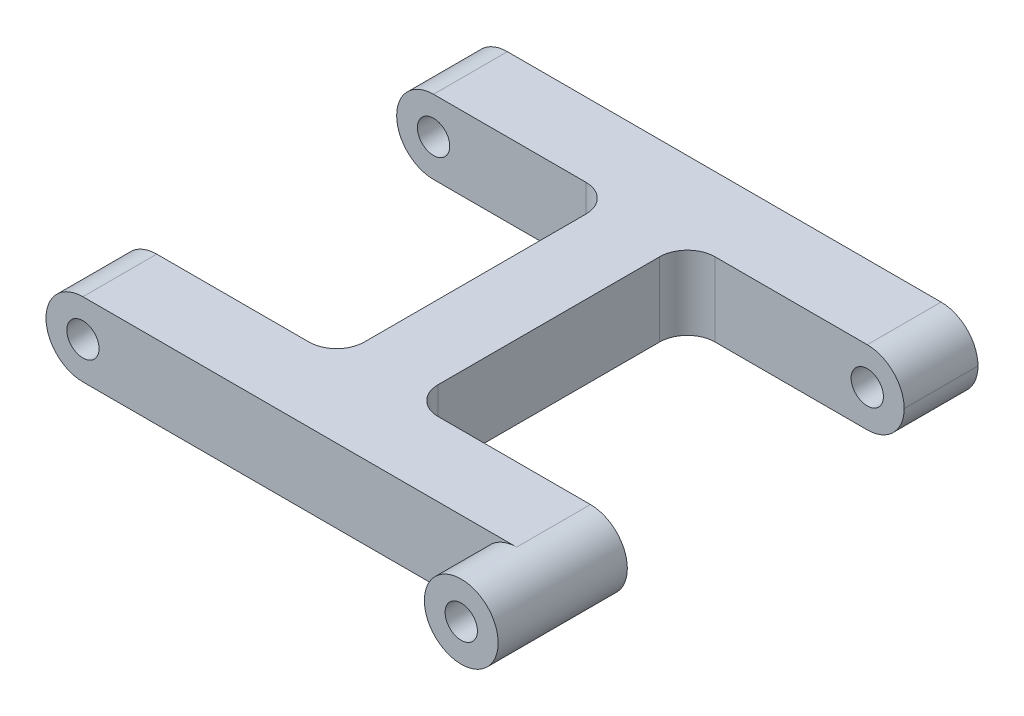
SolidWorks part; units mm, degrees
ref_plane "Alzado" through (0, 0, 0) normal (0, 0, 1) x (1, 0, 0)
ref_plane "Planta" through (0, 0, 0) normal (0, 1, 0) x (1, 0, 0)
ref_plane "Vista lateral" through (0, 0, 0) normal (1, 0, 0) x (0, 0, -1)
sketch "Croquis2" plane through (0, 0, 0) normal (0, 1, 0) x (1, 0, 0)
  line L5 (27.5, -23) -> (27.5, -15)
  line L6 (27.5, -15) -> (4, -15)
  line L7 (4, -15) -> (4, 15)
  line L8 (4, 15) -> (27.5, 15)
  line L9 (27.5, 15) -> (27.5, 23)
  line L24 (-35, 0) -> (35, 0) construction
  line L35 (27.5, 23) -> (-27.5, 23)
  line L36 (27.5, -23) -> (-27.5, -23)
  line L37 (-27.5, -23) -> (-27.5, -15)
  line L38 (-27.5, -15) -> (-4, -15)
  line L39 (-4, -15) -> (-4, 15)
  line L40 (-4, 15) -> (-27.5, 15)
  line L41 (-27.5, 15) -> (-27.5, 23)
  line L42 (0, 23) -> (0, -23) construction
  dimension "D1" = 55
  dimension "D2" = 55
  dimension "D3" = 4
  dimension "D4" = 4
  dimension "D5" = 8
  dimension "D6" = 8
  dimension "D7" = 23.5
  dimension "D8" = 30
  dimension "D9" = 30
extrude "Saliente-Extruir1" add sketch "Croquis2" along normal mid plane 8
sketch "Croquis3" plane through (0, 0, 23) normal (0, 0, 1) x (1, 0, 0)
  line L2 (-27.5, 4) -> (-27.5, -4) construction
  line L5 (27.5, 4) -> (27.5, -4) construction
  line L6 (-27.5, -4) -> (27.5, -4) construction
  circle A0 centre (23.5, 0) radius 1.75
  circle A1 centre (-23.5, 0) radius 1.75
  dimension "D1" = 3.5
  dimension "D2" = 3.5
  dimension "D3" = 4
  dimension "D6" = 4
  dimension "D4" = 4
  dimension "D5" = 4
extrude "Cortar-Extruir1" cut sketch "Croquis3" against normal through all
fillet "Redondeo8" radius 4 8 edges at (27.5, -4, -19) (27.5, 4, -19) (27.5, -4, 19) (27.5, 4, 19) (-27.5, -4, -19) (-27.5, 4, -19) (-27.5, -4, 19) (-27.5, 4, 19)
fillet "Redondeo9" radius 3 4 edges at (4, 0, 15) (4, 0, -15) (-4, 0, 15) (-4, 0, -15)
sketch "Croquis4" plane through (0, 0, 23) normal (0, 0, 1) x (1, 0, 0)
  circle A0 centre (23.5, 0) radius 4
  circle A2 centre (23.5, 0) radius 1.75
  dimension "D1" = 8
extrude "Saliente-Extruir2" add sketch "Croquis4" along normal blind 6
sketch "Croquis5" plane through (0, 0, -23) normal (0, 0, -1) x (-1, 0, 0)
  circle A0 centre (-23.5, 0) radius 3.1
  dimension "D1" = 6.2
extrude "Cortar-Extruir2" cut sketch "Croquis5" against normal blind 3.2
